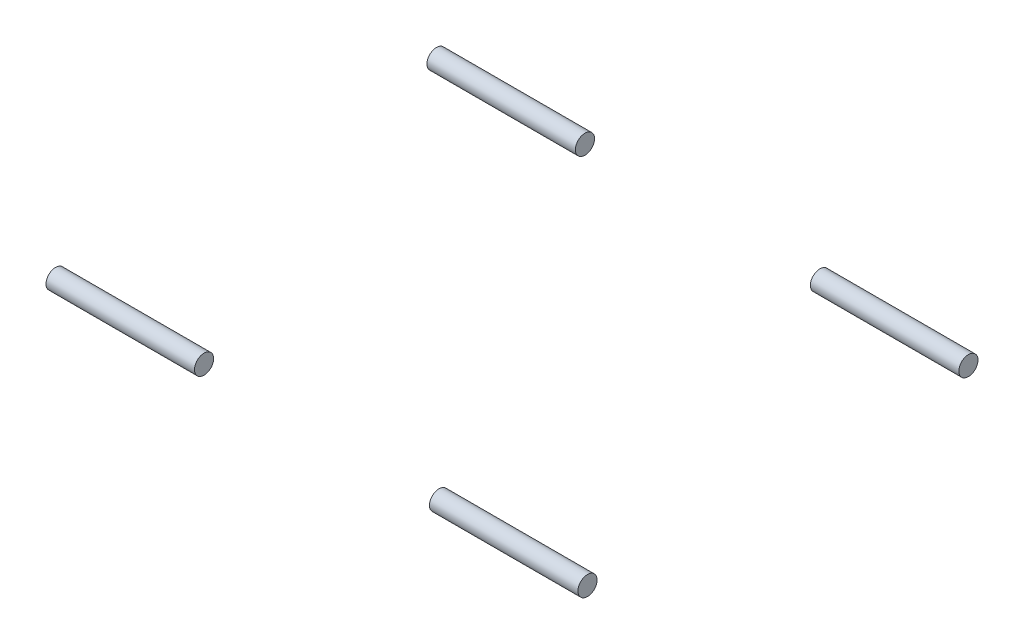
SolidWorks part; units mm, degrees
material "6061-T6 (SS)"
ref_plane "Front Plane" through (0, 0, 0) normal (0, 0, 1) x (1, 0, 0)
ref_plane "Top Plane" through (0, 0, 0) normal (0, 1, 0) x (1, 0, 0)
ref_plane "Right Plane" through (0, 0, 0) normal (1, 0, 0) x (0, 0, -1)
sketch "Sketch1" plane through (88.15, 0, 0) normal (-1, 0, 0) x (0, 0, 1)
  circle A0 centre (126.25, 0) radius 3.175
  circle A1 centre (0, 0) radius 3.175
  circle A2 centre (0, 0) radius 3.175 construction
  circle A3 centre (126.25, 0) radius 3.175 construction
extrude "Boss-Extrude1" add sketch "Sketch1" along normal up to surface (49.2125 mm away)
mirror "Mirror1" about plane through (0, 0, 0) normal (1, 0, 0) of bodies 101 102
